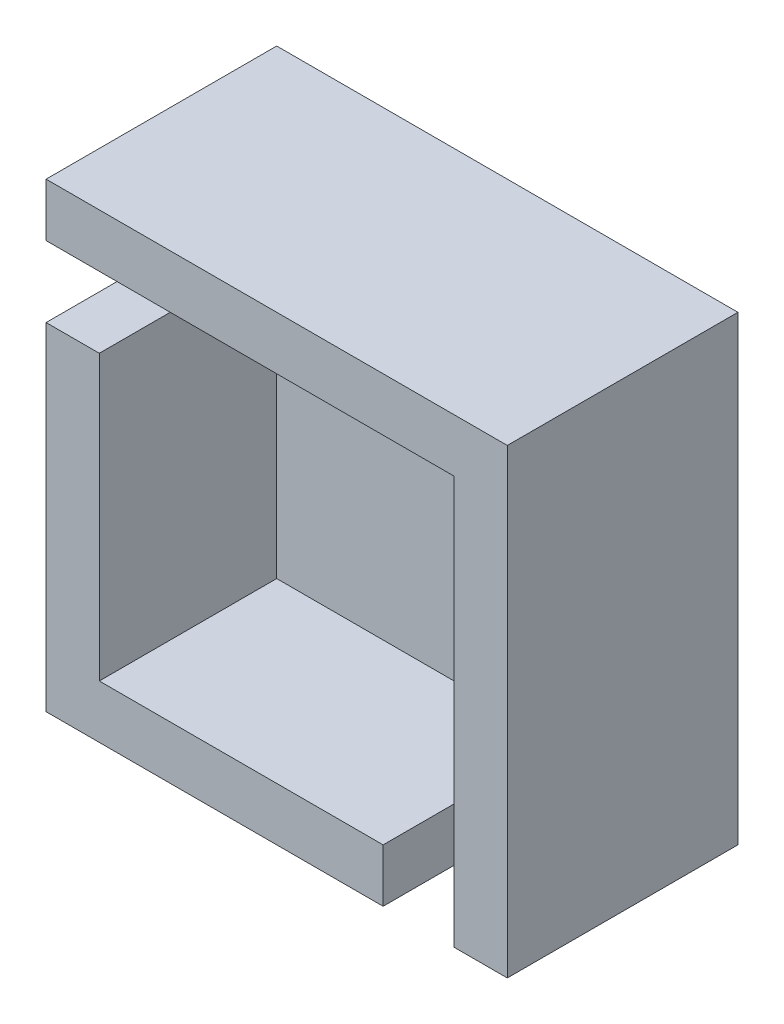
SolidWorks part; units mm, degrees
ref_plane "Front Plane" through (0, 0, 0) normal (0, 0, 1) x (1, 0, 0)
ref_plane "Top Plane" through (0, 0, 0) normal (0, 1, 0) x (1, 0, 0)
ref_plane "Right Plane" through (0, 0, 0) normal (1, 0, 0) x (0, 0, -1)
sketch "Sketch1" plane through (0, 0, 0) normal (0, 0, 1) x (1, 0, 0)
  line L0 (-31.7401, 10.2517) -> (-5.7401, 10.2517)
  line L1 (-5.7401, 10.2517) -> (-5.7401, -15.7483)
  line L2 (-5.7401, -15.7483) -> (-31.7401, -15.7483)
  line L3 (-31.7401, -15.7483) -> (-31.7401, 10.2517)
  dimension "D1" = 26
  dimension "D2" = 26
extrude "Boss-Extrude5" add sketch "Sketch1" along normal blind 3
sketch "Sketch2" plane through (0, 0, 3) normal (0, 0, 1) x (1, 0, 0)
  line L0 (-31.7401, 10.2517) -> (-5.7401, 10.2517)
  line L1 (-5.7401, 10.2517) -> (-31.7401, 10.2517) construction
  line L2 (-5.7401, 10.2517) -> (-5.7401, -15.7483)
  line L3 (-5.7401, -15.7483) -> (-5.7401, 10.2517) construction
  line L4 (-5.7401, -15.7483) -> (-8.7401, -15.7483)
  line L5 (-31.7401, -15.7483) -> (-5.7401, -15.7483) construction
  line L6 (-8.7401, -15.7483) -> (-8.7401, 7.2517)
  line L7 (-8.7401, 7.2517) -> (-31.7401, 7.2517)
  line L8 (-31.7401, 10.2517) -> (-31.7401, -15.7483) construction
  line L9 (-31.7401, 7.2517) -> (-31.7401, 10.2517)
  line L10 (-31.7401, 3.2517) -> (-28.7401, 3.2517)
  line L11 (-28.7401, 3.2517) -> (-28.7401, -12.7483)
  line L12 (-28.7401, -12.7483) -> (-12.7401, -12.7483)
  line L13 (-12.7401, -12.7483) -> (-12.7401, -15.7483)
  line L14 (-12.7401, -15.7483) -> (-31.7401, -15.7483)
  line L15 (-31.7401, -15.7483) -> (-31.7401, 3.2517)
  dimension "D1" = 3
  dimension "D2" = 3
  dimension "D3" = 3
  dimension "D4" = 3
  dimension "D5" = 16
  dimension "D6" = 16
  dimension "D7" = 23
  dimension "D8" = 23
extrude "Boss-Extrude6" add sketch "Sketch2" along normal blind 10
